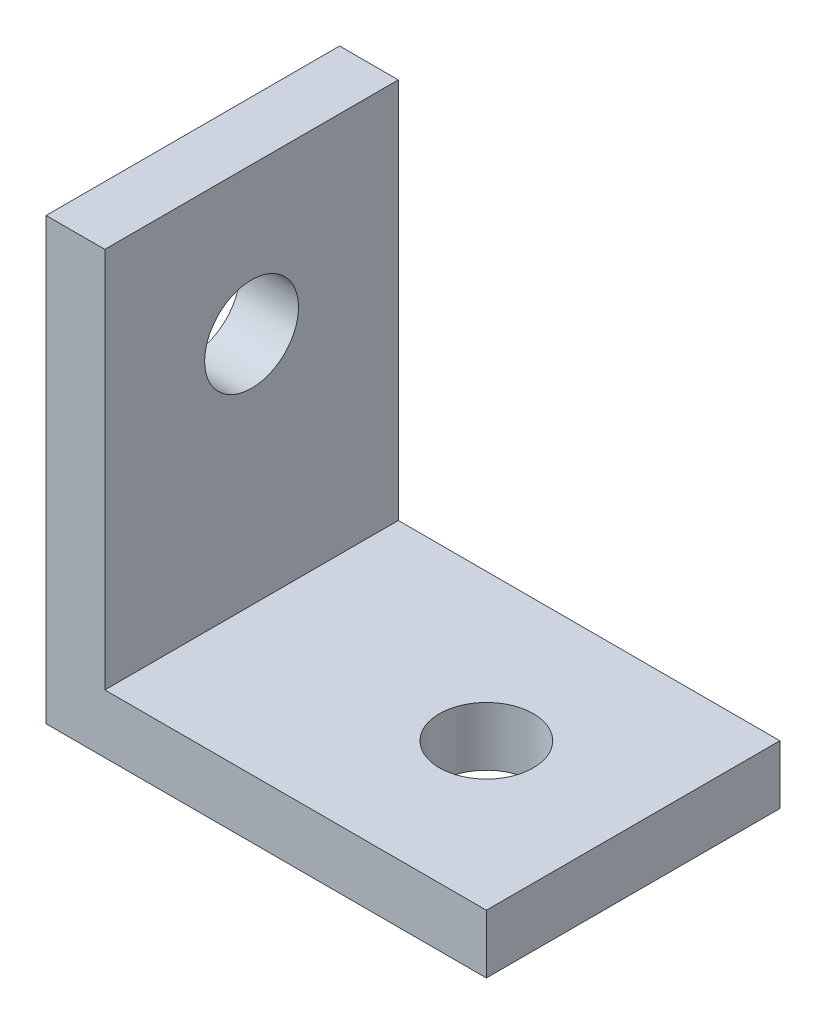
SolidWorks part; units mm, degrees
material "1060 Alloy"
ref_plane "Front Plane" through (0, 0, 0) normal (0, 0, 1) x (1, 0, 0)
ref_plane "Top Plane" through (0, 0, 0) normal (0, 1, 0) x (1, 0, 0)
ref_plane "Right Plane" through (0, 0, 0) normal (1, 0, 0) x (0, 0, -1)
sketch "Sketch1" plane through (0, 0, 0) normal (0, 0, 1) x (1, 0, 0)
  line L0 (0, 0) -> (0, 15)
  line L1 (0, 15) -> (2, 15)
  line L2 (2, 15) -> (2, 2)
  line L3 (2, 2) -> (15, 2)
  line L4 (15, 2) -> (15, 0)
  line L5 (15, 0) -> (0, 0)
  dimension "D1" = 2
  dimension "D2" = 15
extrude "Base" add sketch "Sketch1" along normal mid plane 10
hole_wizard "Ø3.2 (3.2) MountHoles" positions "3DSketch1" profile "Sketch2" hole size "Ø3.2" standard "ANSI Metric" end condition through all
sketch3d "3DSketch1"
  line L0 (0, 0, 5) -> (0, 0, -5) construction
  point P0 (0, 10, 0)
  point P2 (10, 0, 0)
  dimension "D1" = 10
  dimension "D2" = 10
sketch "Sketch2" plane through (0, 10, 0) normal (0, 1, 0) x (0, 0, 1)
  line L0 (0, 0) -> (0, 15)
  line L1 (0, 15) -> (1.6, 15)
  line L2 (1.6, 15) -> (1.6, 0)
  line L5 (1.6, 0) -> (0, 0)
  line L11 (0, -6.35) -> (0, 107.95) construction
  dimension "Thru Hole Dia." = 3.2
  dimension "Thru Hole Depth" = 15
